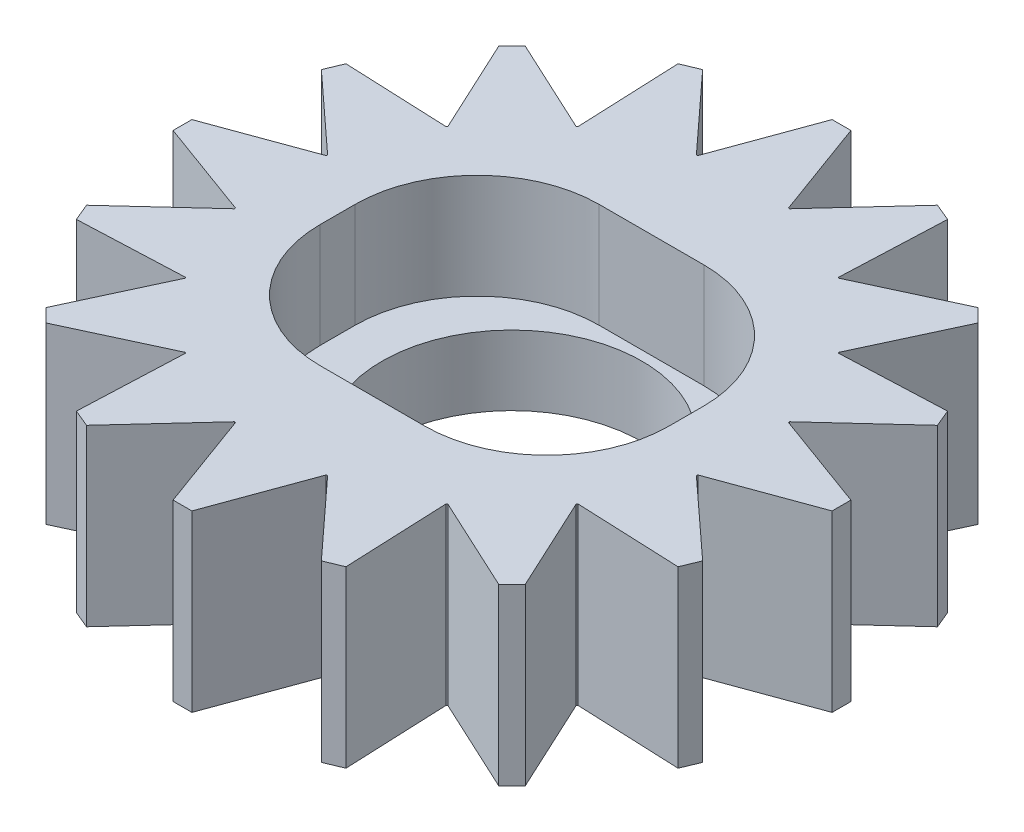
SolidWorks part; units mm, degrees
ref_plane "Front Plane" through (0, 0, 0) normal (0, 0, 1) x (1, 0, 0)
ref_plane "Top Plane" through (0, 0, 0) normal (0, 1, 0) x (1, 0, 0)
ref_plane "Right Plane" through (0, 0, 0) normal (1, 0, 0) x (0, 0, -1)
sketch "Sketch2" plane through (0, 0, 0) normal (0, 1, 0) x (1, 0, 0)
  line L0 (0, 6.75) -> (0, -22.3339) construction
  line L1 (6.75, 0) -> (-25.2541, 0) construction
  circle A0 centre (0, 0) radius 6.75
  dimension "D1" = 13.5
extrude "Boss-Extrude1" add sketch "Sketch2" along normal blind 5
sketch "Sketch3" plane through (0, 5, 0) normal (0, 1, 0) x (1, 0, 0)
  line L1 (-5, 4) -> (5, 4)
  line L2 (-5, 4) -> (-5, -4)
  line L3 (-5, -4) -> (5, -4)
  line L4 (5, 4) -> (5, -4)
  line L5 (-5, 4) -> (5, -4) construction
  line L6 (-5, -4) -> (5, 4) construction
  point P0 (0, 0)
  dimension "D1" = 10
  dimension "D2" = 8
extrude "Cut-Extrude1" cut sketch "Sketch3" against normal blind 3
fillet "Fillet1" radius 3.5 4 edges at (-5, 3.5, 4) (5, 3.5, 4) (-5, 3.5, -4) (5, 3.5, -4)
sketch "Sketch4" plane through (0, 2, 0) normal (0, 1, 0) x (1, 0, 0)
  line L1 (1.5, 4) -> (-1.5, 4) construction
  line L2 (0, 0) -> (0, -17.2909) construction
  circle A0 centre (0, 0) radius 3.725
  dimension "D1" = 7.45
  dimension "D3" = 4
extrude "Cut-Extrude2" cut sketch "Sketch4" against normal through all
ref_plane "Plane1" through (0, 5, 0) normal (0, 1, 0) x (1, 0, 0)
sketch "Sketch5" plane through (0, 5, 0) normal (0, 1, 0) x (1, 0, 0)
  line L0 (0, 0) -> (0, 13.0768) construction
  line L1 (0, 0) -> (17.6113, 0) construction
  line L2 (-1.3001, 6.6236) -> (-0.2697, 9.442)
  line L3 (-0.2697, 9.442) -> (0.2697, 9.442)
  line L4 (0.2697, 9.442) -> (1.3001, 6.6236)
  line L5 (1.3001, 6.6236) -> (-1.3001, 6.6236)
  line L6 (-0.2697, -9.442) -> (-1.3001, -6.6236)
  line L7 (1.3001, -6.6236) -> (0.2697, -9.442)
  line L8 (0.2697, -9.442) -> (-0.2697, -9.442)
  line L9 (-1.3001, -6.6236) -> (1.3001, -6.6236)
  circle A0 centre (0, 0) radius 6.75 construction
  point P126 (0, 0)
  dimension "D1" = 2
extrude "Boss-Extrude2" add sketch "Sketch5" against normal blind 5
pattern_circular "CirPattern1" count 16 over 360 about axis through (0, 2, 0) along (0, 1, 0) of "Boss-Extrude2"
